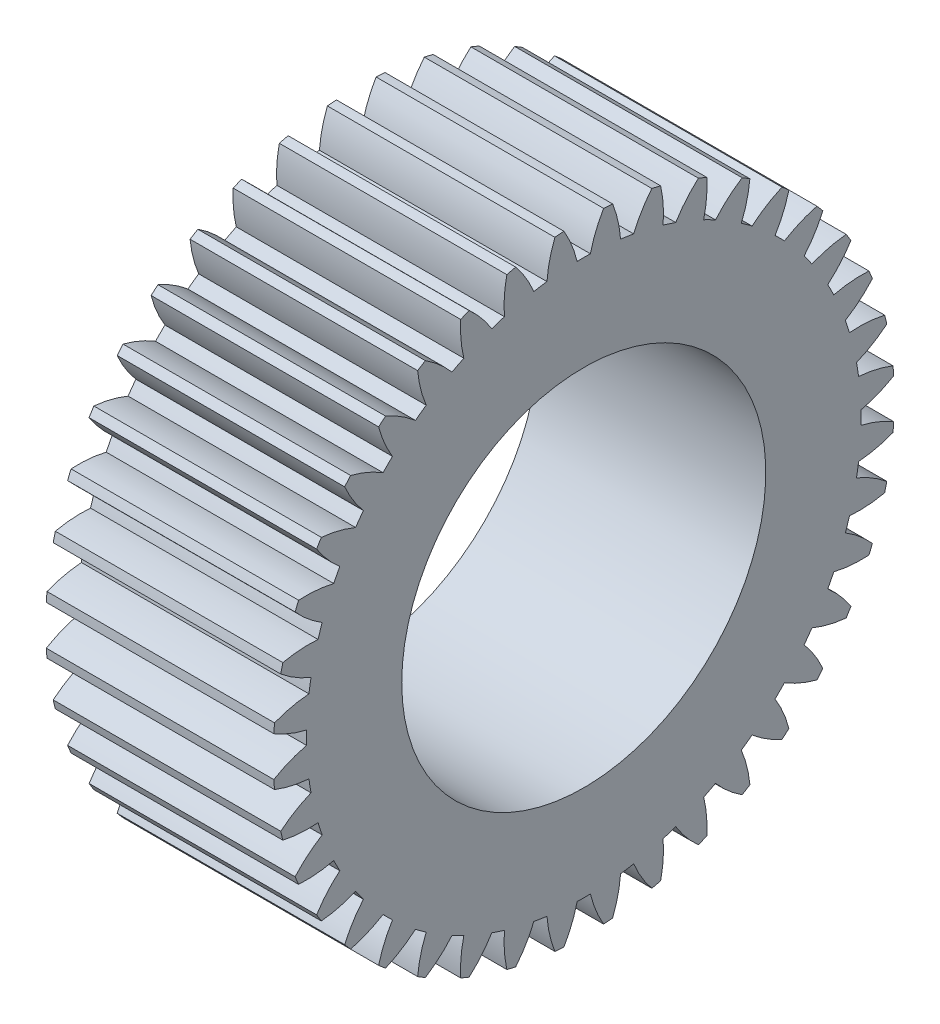
SolidWorks part; units mm, degrees
ref_plane "Plane1" through (0, 0, 0) normal (0, 0, 1) x (1, 0, 0)
ref_plane "Plane2" through (0, 0, 0) normal (0, 1, 0) x (1, 0, 0)
ref_plane "Plane3" through (0, 0, 0) normal (1, 0, 0) x (0, 0, -1)
sketch "HoldingSke" plane through (0, 0, 0) normal (0, 1, 0) x (1, 0, 0)
  line L0 (0, 0) -> (1.1785, -0.9889)
  line L1 (-15, 0) -> (100, 0) construction
  line L2 (0, 0) -> (-2.1039, 2.3779)
  line L3 (0, 0) -> (-11.863, 4.5341)
  line L4 (0, 0) -> (6.6156, 5.5511)
  line L5 (0, 0) -> (-46.8476, -17.4728)
  line L6 (0, 0) -> (-8.2896, -5.593)
  line L7 (-2.1039, 2.3779) -> (8.6586, 51.2059)
  line L8 (-76.2, 54.61) -> (-73.9, 54.61)
  line L9 (-71.009, 38.7566) -> (-53.1078, 45.2721)
  line L10 (-76.2, 71.12) -> (104.1128, 71.12)
  line L11 (0, 0) -> (-10, 0)
  line L12 (-76.2, 101.6) -> (-76.175, 101.6)
  line L13 (24.9733, 27.94) -> (52.9518, 28.4284)
  line L14 (24.9733, 27.94) -> (24.9743, 27.94)
  line L15 (24.9733, 27.94) -> (100.4006, 29.5858)
  line L16 (-63.627, -0.65) -> (-12.827, -0.65)
  circle A0 centre (0, 0) radius 8
  circle A1 centre (0, 0) radius 12.1865
  circle A2 centre (0, 0) radius 37.5
  circle A3 centre (0, 0) radius 8
  dimension "Num_teeth" = 40
  dimension "Pitch_radius" = 180.3128
  dimension "Width" = 10
  dimension "Thickness" = 10
sketch "BasProSke" plane through (0, 0, 0) normal (0, 1, 0) x (1, 0, 0)
  line L0 (-10, 0) -> (60, 0) construction
  line L1 (0, 0) -> (0, 13.65)
  line L2 (0, 0) -> (10, 0)
  line L3 (10, 0) -> (10, 13.65)
  line L4 (10, 13.65) -> (0, 13.65)
  dimension "Thickness" = 10
  dimension "Diameter" = 27.3
revolve "Base-Revolve" add sketch "BasProSke" angle 360 about L0
sketch "TooCutSke" plane through (0, 0, 0) normal (1, 0, 0) x (0, 0, -1)
  line L1 (0, 0) -> (0, 107) construction
  line L2 (0, 0) -> (-0.5541, 12.9882) construction
  line L3 (0, 0) -> (-2.0386, 25.9031) construction
  line L4 (-0.5541, 12.9882) -> (-1.0193, 12.9516) construction
  arc A0 (0.292, 12.183) -> (-0.292, 12.183) centre (0, 0) ccw
  arc A1 (0.8862, 13.6467) -> (-0.8862, 13.6467) centre (0, 0) ccw
  circle A2 centre (0, 0) radius 13 construction
  circle A3 centre (0, 0) radius 12.216 construction
  arc A4 (-0.292, 12.183) -> (-0.8862, 13.6467) centre (-5.3513, 10.9815) ccw
  arc A5 (0.8862, 13.6467) -> (0.292, 12.183) centre (5.3513, 10.9815) ccw
extrude "ToothCut" cut sketch "TooCutSke" along normal through all
fillet "Breaks" [suppressed] radius 0.013 tangent propagation no
fillet "RootFillets" [suppressed] radius 0.1635
pattern_circular "TeethCuts" count 40 every 9 about axis through (-10, 0, 0) along (1, 0, 0) of "ToothCut", "RootFillets", "Breaks"
sketch "HubNeaOneSke" plane through (0, 0, 0) normal (-1, 0, 0) x (0, 0, 1)
  circle A0 centre (0, 0) radius 12.1865
  dimension "Diameter" = 24.373
extrude "HubNearOne" [suppressed] add sketch "HubNeaOneSke" along normal blind 40.0001
sketch "HubNeaBotSke" plane through (0, 0, 0) normal (-1, 0, 0) x (0, 0, 1)
  circle A0 centre (0, 0) radius 12.1865
  dimension "Diameter" = 24.373
extrude "HubNearBoth" [suppressed] add sketch "HubNeaBotSke" along normal blind 20
ref_plane "FarPln" through (10, 0, 0) normal (1, 0, 0) x (0, 0, -1)
sketch "HubFarSke" plane through (10, 0, 0) normal (1, 0, 0) x (0, 0, -1)
  circle A0 centre (0, 0) radius 12.1865
  dimension "Diameter" = 24.373
extrude "HubFar" [suppressed] add sketch "HubFarSke" along normal blind 20
sketch "BorSke" plane through (0, 0, 0) normal (1, 0, 0) x (0, 0, -1)
  circle A0 centre (0, 0) radius 8
  dimension "Diameter" = 16
extrude "Bore" cut sketch "BorSke" along normal mid plane 100.0001
sketch "KeySke" plane through (0, 0, 0) normal (1, 0, 0) x (0, 0, -1)
  line L0 (-2.5, 0) -> (-2.5, 10.3)
  line L1 (-2.5, 10.3) -> (2.5, 10.3)
  line L2 (2.5, 10.3) -> (2.5, 0)
  line L3 (0, 0) -> (0, 34) construction
  line L4 (-2.5, 0) -> (2.5, 0)
  dimension "Width" = 5
extrude "Keyway" [suppressed] cut sketch "KeySke" along normal mid plane 100.0001
pattern_circular "Keyway2" [suppressed] count 2 every 90 about axis through (-10, 0, 0) along (1, 0, 0) reverse direction yes
equation "' \"Module@HoldingSke\" = 6.35"
equation "' \"Num_teeth@HoldingSke\" = 12"
equation "' \"Ap@HoldingSke\" =  20"
equation "' \"Ap@HoldingSke\" = 20"
equation "' \"Width@HoldingSke\" = 0.5 * 25.4"
equation "' \"Hub_dia@HoldingSke\"= 1 * 25.4"
equation "' \"Hub_dia@HoldingSke\" = 1 * 25.4"
equation "' \"Overall_len@HoldingSke\" = 1.0 * 25.4"
equation "' \"Bore@HoldingSke\" = 0.75 * 25.4"
equation "' \"T_dim@HoldingSke\" = 0.1 * 25.4"
equation "' \"Width@KeySke\" = 0.25 * 25.4"
equation "' \"Show_teeth@HoldingSke\" = 13"
equation "' \"Backlash@HoldingSke\" = 0.009 * 25.4"
equation "' \"Addendum_fac@HoldingSke\" = 1.0"
equation "' \"Dedendum_fac@HoldingSke\" = 1.25"
equation "' \"Dedendum_add@HoldingSke\" = 0.00005 * 25.4"
equation "' \"Clearance_fac@HoldingSke\" = 0.25"
equation "\"Pitch@HoldingSke\" = 1 / \"Module@HoldingSke\""
equation "\"Overcut_dia@TooCutSke\" = (\"Num_teeth@HoldingSke\" + 2 * \"Addendum_fac@HoldingSke\") / \"Pitch@HoldingSke\" + 0.002 * 25.4"
equation "\"Pitch_dia@TooCutSke\" = \"Num_teeth@HoldingSke\" / \"Pitch@HoldingSke\""
equation "\"Base_dia@TooCutSke\" = \"Num_teeth@HoldingSke\" / \"Pitch@HoldingSke\" * cos((\"Ap@HoldingSke\"  * 3.14159265 / 180))"
equation "\"Root_dia@TooCutSke\" = (\"Num_teeth@HoldingSke\" + 2) / \"Pitch@HoldingSke\" - 2 * (\"Addendum_fac@HoldingSke\" + \"Dedendum_fac@HoldingSke\") / \"Pitch@HoldingSke\" - \"Dedendum_add@HoldingSke\" * 2"
equation "\"Half_ang@TooCutSke\" = 180 / \"Num_teeth@HoldingSke\""
equation "\"Half_CT@TooCutSke\" = \"Num_teeth@HoldingSke\" / \"Pitch@HoldingSke\" * sin((3.14159265 / 2 / \"Num_teeth@HoldingSke\")) / 2 - 7 * \"Backlash@HoldingSke\" / 4"
equation "\"Flank_rad@TooCutSke\" = \"Num_teeth@HoldingSke\" / \"Pitch@HoldingSke\" / 5"
equation "\"Radius@RootFillets\" = \"Clearance_fac@HoldingSke\" / \"Pitch@HoldingSke\" + \"Dedendum_add@HoldingSke\""
equation "\"Break_rad@Breaks\" = 0.02 / \"Pitch@HoldingSke\""
equation "\"Thickness@HoldingSke\" = \"Width@HoldingSke\""
equation "\"OAL@HoldingSke\" = \"Thickness@HoldingSke\""
equation "\"MHD@HoldingSke\" = (\"Num_teeth@HoldingSke\" + 2) / \"Pitch@HoldingSke\" - 2 * (\"Addendum_fac@HoldingSke\" + \"Dedendum_fac@HoldingSke\")  / \"Pitch@HoldingSke\" - \"Dedendum_add@HoldingSke\" * 2"
equation "\"MBD@HoldingSke\" = (\"Num_teeth@HoldingSke\" + 2) / \"Pitch@HoldingSke\" - 2 * (\"Addendum_fac@HoldingSke\" + \"Dedendum_fac@HoldingSke\")  / \"Pitch@HoldingSke\" - \"Dedendum_add@HoldingSke\" * 2 - 0.002 * 25.4"
equation "\"MHD@HoldingSke\" = ((sgn( \"MHD@HoldingSke\" - \"Hub_dia@HoldingSke\" )-1)*( \"MHD@HoldingSke\" - \"Hub_dia@HoldingSke\" ))/-2+ \"Hub_dia@HoldingSke\""
equation "\"MBD@HoldingSke\" = ((sgn( \"MBD@HoldingSke\" - \"Bore@HoldingSke\" )-1)*( \"MBD@HoldingSke\" - \"Bore@HoldingSke\" ))/-2+ \"Bore@HoldingSke\""
equation "\"OAL@HoldingSke\" = ((sgn( \"OAL@HoldingSke\" - \"Overall_len@HoldingSke\" )+1)*( \"OAL@HoldingSke\" - \"Overall_len@HoldingSke\" ))/2 + \"Overall_len@HoldingSke\" + 0.000002 * 25.4"
equation "\"Num_teeth@TeethCuts\" = int( \"Show_teeth@HoldingSke\" ) + 1"
equation "\"Num_teeth@TeethCuts\" = ((sgn( \"Num_teeth@TeethCuts\" - \"Num_teeth@HoldingSke\" )-1)*( \"Num_teeth@TeethCuts\" - \"Num_teeth@HoldingSke\" ))/-2+ \"Num_teeth@HoldingSke\""
equation "\"Num_teeth@TeethCuts\" = ((sgn( \"Num_teeth@TeethCuts\" - 2.0)+1)*( \"Num_teeth@TeethCuts\" - 2.0))/2 +2.0"
equation "\"Angle@TeethCuts\" = 360.0 / \"Num_teeth@HoldingSke\""
equation "\"Diameter@BasProSke\" = (\"Num_teeth@HoldingSke\" + 2 * \"Addendum_fac@HoldingSke\") / \"Pitch@HoldingSke\""
equation "\"Thickness@BasProSke\"  = \"Thickness@HoldingSke\""
equation "' \"Fillet_rad@BasProSke\" =  \"Thickness@HoldingSke\" * 0.05"
equation "' \"Fillet_rad@BasProSke\" = \"Thickness@HoldingSke\" * 0.05"
equation "\"MHD@HoldingSke\" = ((sgn( \"MHD@HoldingSke\" - \"Root_dia@TooCutSke\" )-1)*( \"MHD@HoldingSke\" - \"Root_dia@TooCutSke\" ))/-2+ \"Root_dia@TooCutSke\""
equation "\"Diameter@HubNeaOneSke\" = \"MHD@HoldingSke\""
equation "\"Length@HubNearOne\" = \"OAL@HoldingSke\" - \"Thickness@BasProSke\""
equation "\"Diameter@HubNeaBotSke\" = \"MHD@HoldingSke\""
equation "\"Length@HubNearBoth\" = ( \"OAL@HoldingSke\" - \"Thickness@BasProSke\" ) / 2.0"
equation "\"Thickness@FarPln\" = \"Thickness@BasProSke\""
equation "\"Diameter@HubFarSke\" = \"MHD@HoldingSke\""
equation "\"Length@HubFar\" = ( \"OAL@HoldingSke\" - \"Thickness@BasProSke\" ) / 2.0"
equation "\"Diameter@BorSke\" = \"MBD@HoldingSke\""
equation "\"D1@Bore\" = \"OAL@HoldingSke\" * 2.0"
equation "\"D1@Keyway\" = \"OAL@HoldingSke\" * 2.0"
equation "\"Offset@KeySke\" = \"T_dim@HoldingSke\" + \"MBD@HoldingSke\" / 2.0"
